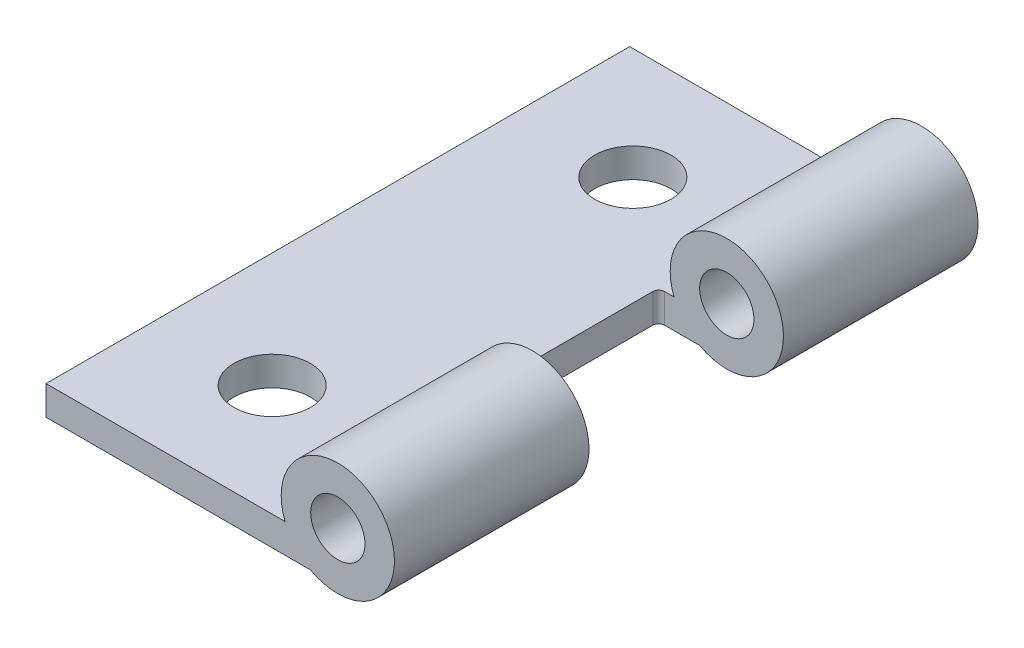
SolidWorks part; units mm, degrees
ref_plane "Front Plane" through (0, 0, 0) normal (0, 0, 1) x (1, 0, 0)
ref_plane "Top Plane" through (0, 0, 0) normal (0, 1, 0) x (1, 0, 0)
ref_plane "Right Plane" through (0, 0, 0) normal (1, 0, 0) x (0, 0, -1)
sketch "Sketch2" plane through (0, 0, 0) normal (0, 0, 1) x (1, 0, 0)
  line L4 (-2.4638, 4.7768) -> (-2.4638, 2.6146) construction
  line L5 (-2.4638, 2.6146) -> (-2.4638, -7.2406) construction
  line L6 (-17.6276, 2.6146) -> (-17.6276, 3.8846)
  line L7 (-17.6276, 3.8846) -> (-7.2242, 3.8846)
  line L8 (-17.6276, 2.6146) -> (-6.1087, 2.6146)
  circle A2 centre (-4.9276, 4.7768) radius 1.1811
  arc A3 (-6.1087, 2.6146) -> (-7.2242, 3.8846) centre (-4.9276, 4.7768) ccw
  point P11 (-12.7, 2.6146)
  point P17 (-12.7, 3.8846)
  point P18 (-2.4638, 4.7768)
extrude "Boss-Extrude1" add sketch "Sketch2" along normal blind 12.7 and the other way blind 12.7
sketch "Sketch3" plane through (0, 0, 0) normal (0, 0, 1) x (1, 0, 0)
  circle A0 centre (-4.9276, 4.7768) radius 2.4638
extrude "Cut-Extrude1" cut sketch "Sketch3" against normal blind 4.2291 and the other way blind 4.2329
sketch "Sketch4" plane through (0, 0, 0) normal (0, 0, 1) x (1, 0, 0)
  line L0 (-17.6276, 2.6146) -> (-6.1087, 2.6146) construction
  line L1 (-7.8918, 2.6146) -> (-4.986, 2.6146)
  line L2 (-7.8918, 2.6146) -> (-7.8918, 4.8738)
  line L3 (-7.8918, 4.8738) -> (-4.986, 4.8738)
  line L4 (-4.986, 2.6146) -> (-4.986, 4.8738)
  line L5 (-17.6276, 3.8846) -> (-17.6276, 2.6146) construction
  dimension "D1" = 9.7358
extrude "Cut-Extrude2" cut sketch "Sketch4" against normal blind 4.2291 and the other way blind 4.2291
fillet "Fillet2" radius 0.254 1 edges at (-7.8918, 3.2496, -4.2291)
fillet "Fillet3" radius 0.254 1 edges at (-7.8918, 3.2496, 4.2291)
sketch "Sketch5" plane through (0, 3.8846, 0) normal (0, 1, 0) x (1, 0, 0)
  line L0 (-17.6276, 12.7) -> (-17.6276, -12.7) construction
  line L1 (-7.2242, 12.7) -> (-17.6276, 12.7) construction
  line L2 (-7.2242, -12.7) -> (-17.6276, -12.7) construction
  circle A0 centre (-12.6365, 7.8486) radius 1.6637
  circle A1 centre (-12.6365, -7.8486) radius 1.6637
  dimension "D3" = 3.3274
  dimension "D5" = 3.3274
  dimension "D1" = 4.9911
  dimension "D2" = 4.8514
  dimension "D4" = 4.8514
extrude "Cut-Extrude3" cut sketch "Sketch5" against normal blind 2.54
